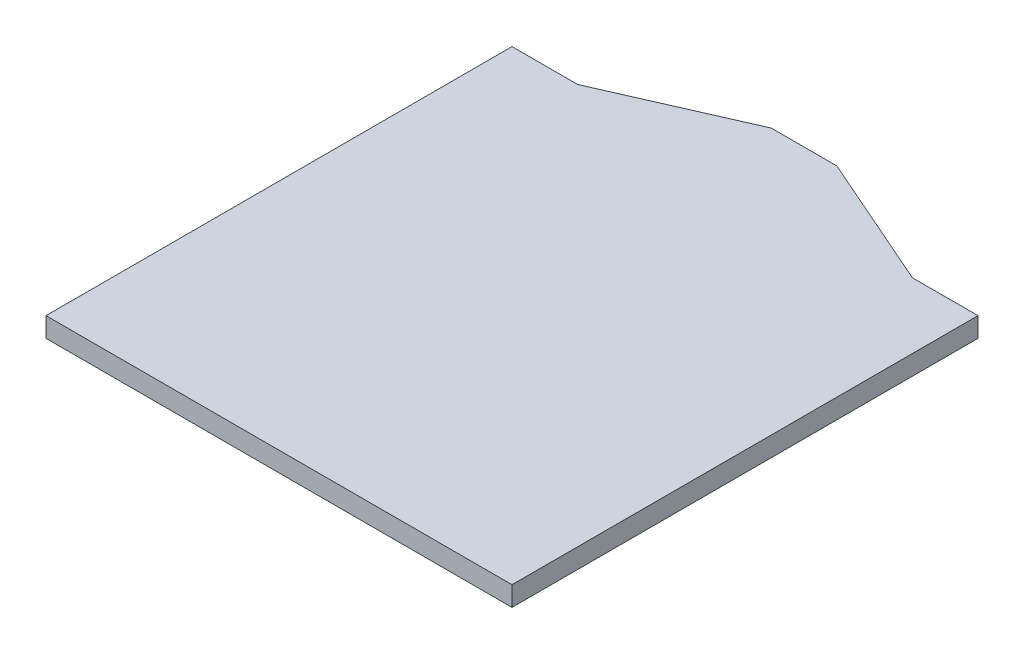
SolidWorks part; units mm, degrees
ref_plane "Front Plane" through (0, 0, 0) normal (0, 0, 1) x (1, 0, 0)
ref_plane "Top Plane" through (0, 0, 0) normal (0, 1, 0) x (1, 0, 0)
ref_plane "Right Plane" through (0, 0, 0) normal (1, 0, 0) x (0, 0, -1)
sketch "Sketch1" plane through (0, 0, 0) normal (0, 1, 0) x (1, 0, 0)
  line L0 (-35.5, 35.5) -> (-25.5, 35.5)
  line L1 (-35.5, 35.5) -> (35.5, 35.5)
  line L2 (-35.5, 35.5) -> (-35.5, -35.5)
  line L3 (-35.5, -35.5) -> (35.5, -35.5)
  line L4 (35.5, 35.5) -> (35.5, -35.5)
  line L5 (-25.5, 35.5) -> (-5, 44.5)
  line L6 (-5, 44.5) -> (5, 44.5)
  line L7 (5, 44.5) -> (25.5, 35.5)
  line L8 (25.5, 35.5) -> (35.5, 35.5)
  point P4 (-35.5, 0)
  point P6 (0, -35.5)
  point P11 (0, 44.5)
  point P12 (0, 35.5)
  dimension "D1" = 71
  dimension "D2" = 71
  dimension "D3" = 10
  dimension "D4" = 80
  dimension "D5" = 10
  dimension "D6" = 10
extrude "Boss-Extrude1" add sketch "Sketch1" along normal blind 3 contours L7 L6 L5 L1 | L4 L1 L0 L2 L3 region at (0, 0, 0) region at (0, 0, -38.9918)
